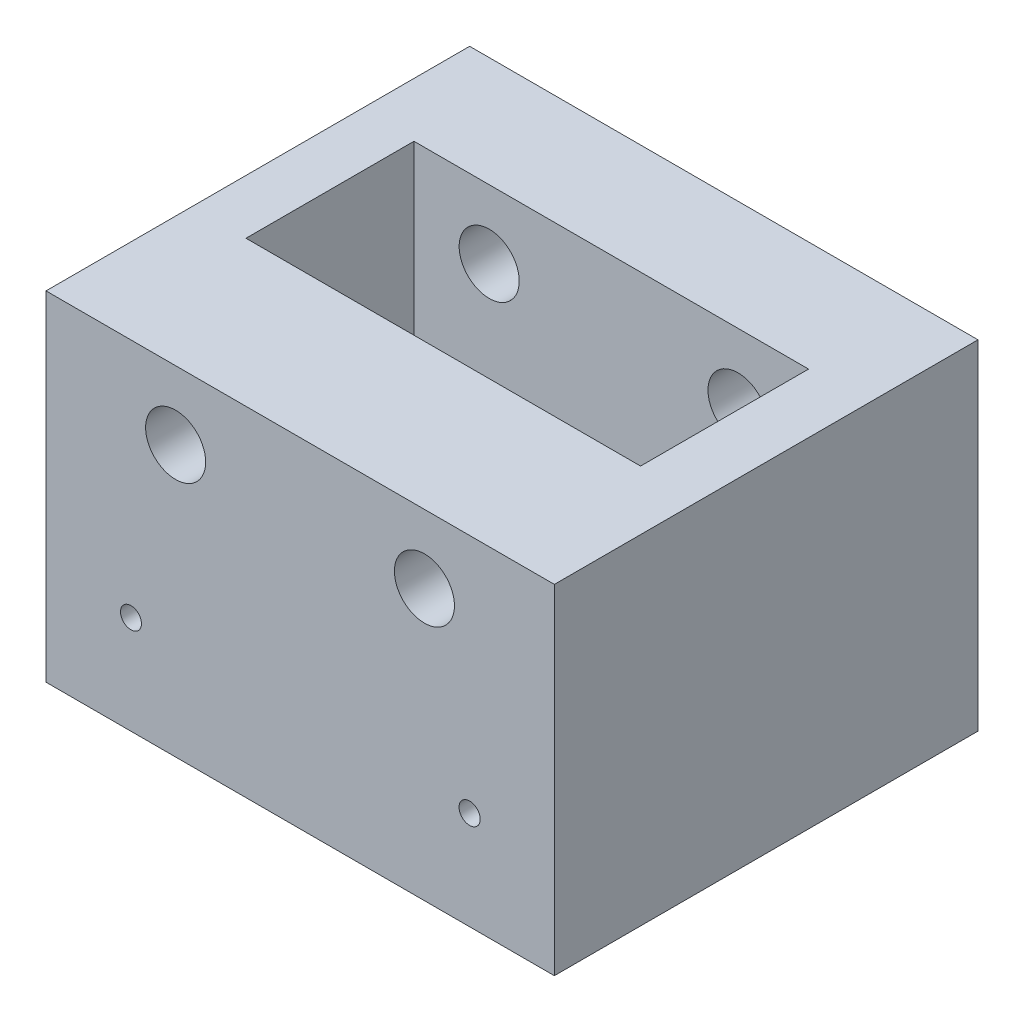
SolidWorks part; units mm, degrees
ref_plane "Front Plane" through (0, 0, 0) normal (0, 0, 1) x (1, 0, 0)
ref_plane "Top Plane" through (0, 0, 0) normal (0, 1, 0) x (1, 0, 0)
ref_plane "Right Plane" through (0, 0, 0) normal (1, 0, 0) x (0, 0, -1)
sketch "Sketch2" plane through (0, 0, 0) normal (0, 0, 1) x (1, 0, 0)
  line L0 (-38.9521, 81.0614) -> (0, 81.0614)
  line L1 (-152.4, 101.6) -> (0, 101.6)
  line L2 (-152.4, 101.6) -> (-152.4, 0)
  line L3 (-152.4, 0) -> (0, 0)
  line L4 (0, 101.6) -> (0, 0)
  line L5 (-20.32, 49.8791) -> (-132.08, 49.8791)
  line L6 (-20.32, 49.8791) -> (-20.32, 9.2391)
  line L7 (-20.32, 9.2391) -> (-132.08, 9.2391)
  line L8 (-132.08, 49.8791) -> (-132.08, 9.2391)
  line L9 (-113.538, 81.0614) -> (-152.4, 81.0614)
  line L10 (-76.2, 9.2391) -> (-76.2, 49.8791)
  line L11 (-76.2, 29.4837) -> (-25.4, 29.4837)
  line L12 (-76.2, 29.4837) -> (-126.9236, 29.4837)
  circle A0 centre (-113.538, 81.0614) radius 9
  circle A1 centre (-38.9521, 81.0614) radius 9
  circle A2 centre (-25.4, 29.4837) radius 3.175
  circle A3 centre (-126.9236, 29.4837) radius 3.1422
  point P4 (-76.2, 9.2391)
  point P6 (-76.2, 0)
  dimension "D5" = 18
  dimension "D6" = 18
  dimension "D10" = 6.35
  dimension "D1" = 152.4
  dimension "D2" = 101.6
  dimension "D3" = 111.76
  dimension "D4" = 40.64
  dimension "D7" = 38.9521
  dimension "D8" = 38.862
  dimension "D9" = 50.8
extrude "Boss-Extrude1" add sketch "Sketch2" along normal blind 127 contours A1 L4 L1 L2 A0 L3 L8 L5 L6 L7 | A3 L10 L5 L8 L7 | A2 L10 L7 L6 L5 region at (-76.1978, 58.5709, 0) region at (-48.5833, 29.5602, 0) region at (-103.8245, 29.5602, 0)
sketch "Sketch3" plane through (0, 101.6, 0) normal (0, 1, 0) x (1, 0, 0)
  line L0 (-76.9406, -32.9999) -> (-76.9406, 0)
  line L1 (-136.0858, -32.9999) -> (-17.7955, -32.9999)
  line L2 (-136.0858, -32.9999) -> (-136.0858, -83.3632)
  line L3 (-136.0858, -83.3632) -> (-17.7955, -83.3632)
  line L4 (-17.7955, -32.9999) -> (-17.7955, -83.3632)
  line L5 (-152.4, 0) -> (0, 0) construction
  line L6 (-76.9406, -83.3632) -> (-76.9406, -127)
  line L7 (-152.4, -127) -> (0, -127) construction
  dimension "D1" = 32.9999
extrude "Cut-Extrude1" cut sketch "Sketch3" against normal blind 159.258 contours L4 L1 L2 L3 region at (-76.9406, 101.6, 58.1816)
